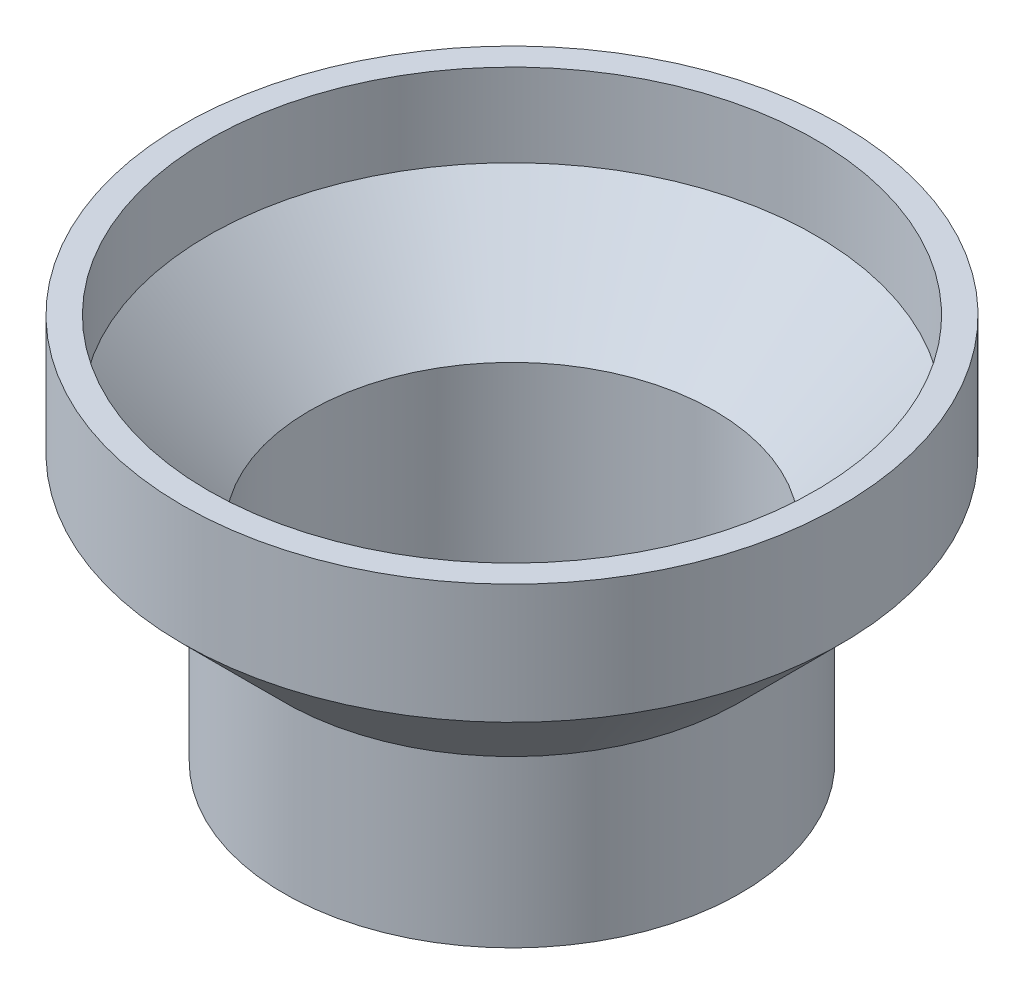
SolidWorks part; units mm, degrees
ref_plane "Front Plane" through (0, 0, 0) normal (0, 0, 1) x (1, 0, 0)
ref_plane "Top Plane" through (0, 0, 0) normal (0, 1, 0) x (1, 0, 0)
ref_plane "Right Plane" through (0, 0, 0) normal (1, 0, 0) x (0, 0, -1)
sketch "Sketch1" plane through (0, 0, 0) normal (0, 1, 0) x (1, 0, 0)
  circle A0 centre (0, 0) radius 15.748
  circle A1 centre (0, 0) radius 13.97
extrude "Boss-Extrude1" add sketch "Sketch1" along normal blind 19.05
sketch "Sketch2" plane through (0, 19.05, 0) normal (0, 1, 0) x (1, 0, 0)
  circle A0 centre (0, 0) radius 22.733
  circle A1 centre (0, 0) radius 13.97
extrude "Boss-Extrude2" add sketch "Sketch2" along normal blind 7.62
sketch "Sketch3" plane through (0, 26.67, 0) normal (0, 1, 0) x (1, 0, 0)
  circle A0 centre (0, 0) radius 20.955
extrude "Cut-Extrude1" cut sketch "Sketch3" against normal blind 5.08
chamfer "Chamfer1" distance 7.62 angle 45 1 edges at (0, 19.05, 15.748)
chamfer "Chamfer2" distance 7.62 angle 45 1 edges at (0, 21.59, 13.97)
